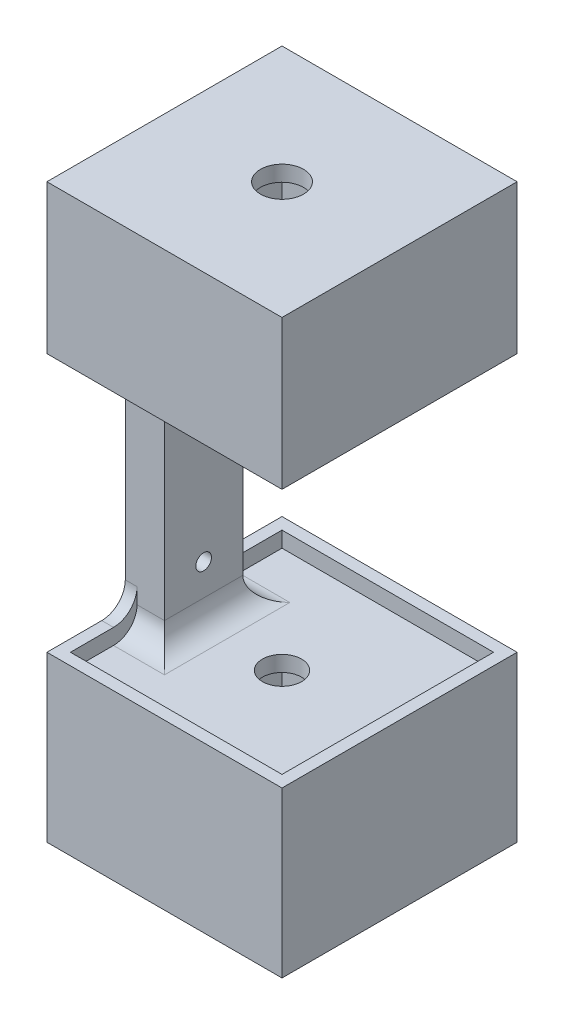
SolidWorks part; units mm, degrees
ref_plane "Спереди" through (0, 0, 0) normal (0, 0, 1) x (1, 0, 0)
ref_plane "Сверху" through (0, 0, 0) normal (0, 1, 0) x (1, 0, 0)
ref_plane "Справа" through (0, 0, 0) normal (1, 0, 0) x (0, 0, -1)
sketch "Эскиз2" plane through (0, 0, 0) normal (0, 1, 0) x (1, 0, 0)
  line L1 (-15, 15) -> (15, 15)
  line L2 (-15, 15) -> (-15, -15)
  line L3 (-15, -15) -> (15, -15)
  line L4 (15, 15) -> (15, -15)
  line L5 (-15, 15) -> (15, -15) construction
  line L6 (-15, -15) -> (15, 15) construction
  point P0 (0, 0)
  dimension "D1" = 30
  dimension "D2" = 30
extrude "Бобышка-Вытянуть1" add sketch "Эскиз2" along normal blind 2
sketch "Эскиз3" plane through (0, 0, 0) normal (0, -1, 0) x (1, 0, 0)
  line L1 (-15, 15) -> (15, 15)
  line L2 (-15, 15) -> (-15, -15)
  line L3 (-15, -15) -> (15, -15)
  line L4 (15, 15) -> (15, -15)
  line L5 (-15, 15) -> (15, -15) construction
  line L6 (-15, -15) -> (15, 15) construction
  point P0 (0, 0)
extrude "Вытянуть-Тонкостенный2" add sketch "Эскиз3" along normal blind 15 thin thin type one direction reverse wall 2
sketch "Эскиз4" plane through (0, 2, 0) normal (0, 1, 0) x (1, 0, 0)
  line L1 (-13.5, 13.5) -> (13.5, 13.5)
  line L2 (-13.5, 13.5) -> (-13.5, -13.5)
  line L3 (-13.5, -13.5) -> (13.5, -13.5)
  line L4 (13.5, 13.5) -> (13.5, -13.5)
  line L5 (-13.5, 13.5) -> (13.5, -13.5) construction
  line L6 (-13.5, -13.5) -> (13.5, 13.5) construction
  point P0 (0, 0)
  dimension "D1" = 27
  dimension "D2" = 27
extrude "Вытянуть-Тонкостенный3" add sketch "Эскиз4" along normal blind 2 thin thin type one direction wall 1.5
sketch "Эскиз5" plane through (0, 2, 0) normal (0, 1, 0) x (1, 0, 0)
  line L1 (-15, 5) -> (-10, 5)
  line L2 (-15, 5) -> (-15, -5)
  line L3 (-15, -5) -> (-10, -5)
  line L4 (-10, 5) -> (-10, -5)
  line L5 (-15, 5) -> (-10, -5) construction
  line L6 (-15, -5) -> (-10, 5) construction
  point P0 (-12.5, 0)
  point P5 (0, 0)
  dimension "D1" = 5
  dimension "D2" = 10
  dimension "D3" = 12.5
extrude "Бобышка-Вытянуть2" add sketch "Эскиз5" along normal blind 35
sketch "Эскиз6" plane through (-15, 0, 0) normal (-1, 0, 0) x (0, 0, 1)
  line L0 (-5, 37) -> (5, 37) construction
  line L1 (-5, 2) -> (5, 2) construction
  circle A0 centre (0, 29) radius 1
  circle A1 centre (0, 9) radius 1
  point P6 (0, 0)
  dimension "D1" = 2
  dimension "D2" = 2
  dimension "D3" = 20
  dimension "D4" = 8
  dimension "D5" = 7
extrude "Вырез-Вытянуть1" cut sketch "Эскиз6" against normal through all
sketch "Эскиз8" plane through (0, 2, 0) normal (0, 1, 0) x (1, 0, 0)
  circle A0 centre (0, 0) radius 2.5
  point P2 (4.7083, 2.9628)
  point P3 (0, 0)
  dimension "D1" = 5
extrude "Вырез-Вытянуть2" cut sketch "Эскиз8" against normal through all
fillet "Скругление1" radius 3 3 edges at (-10, 2, 0) (-11.75, 2, -5) (-11.75, 2, 5)
fillet "Скругление2" radius 3 2 edges at (-14.25, 4, -5.1716) (-14.25, 4, 5.1716)
sketch "Эскиз9" plane through (0, 37, 0) normal (0, 1, 0) x (1, 0, 0)
  line L1 (-15, 15) -> (15, 15)
  line L2 (-15, 15) -> (-15, -15)
  line L3 (-15, -15) -> (15, -15)
  line L4 (15, 15) -> (15, -15)
  line L5 (-15, 15) -> (15, -15) construction
  line L6 (-15, -15) -> (15, 15) construction
  point P0 (0, 0)
extrude "Бобышка-Вытянуть3" add sketch "Эскиз9" along normal blind 2
sketch "Эскиз10" plane through (0, 39, 0) normal (0, 1, 0) x (1, 0, 0)
  line L1 (-15, 15) -> (15, 15)
  line L2 (-15, 15) -> (-15, -15)
  line L3 (-15, -15) -> (15, -15)
  line L4 (15, 15) -> (15, -15)
  line L5 (-15, 15) -> (15, -15) construction
  line L6 (-15, -15) -> (15, 15) construction
  point P0 (0, 0)
extrude "Вытянуть-Тонкостенный4" add sketch "Эскиз10" along normal blind 15 thin thin type one direction reverse wall 2
sketch "Эскиз11" plane through (0, 39, 0) normal (0, 1, 0) x (1, 0, 0)
  circle A0 centre (0, 0) radius 1.75
  dimension "D1" = 3.5
extrude "Вырез-Вытянуть3" cut sketch "Эскиз11" against normal blind 3
fillet "Скругление3" radius 3 3 edges at (-12.5, 37, -5) (-10, 37, 0) (-12.5, 37, 5)
sketch "Эскиз12" plane through (-15, 0, 0) normal (-1, 0, 0) x (0, 0, 1)
  line L1 (-18.8022, 54) -> (-18.8022, -15.0327)
  dimension "D1" = 69.0327
sketch "Эскиз13" plane through (0, -15, 0) normal (0, -1, 0) x (1, 0, 0)
  line L1 (-15, 15) -> (15, 15)
  line L2 (-15, 15) -> (-15, -15)
  line L3 (-15, -15) -> (15, -15)
  line L4 (15, 15) -> (15, -15)
  line L5 (-15, 15) -> (15, -15) construction
  line L6 (-15, -15) -> (15, 15) construction
  point P0 (0, 0)
extrude "Бобышка-Вытянуть4" add sketch "Эскиз13" along normal blind 2
sketch "Эскиз14" plane through (0, 54, 0) normal (0, 1, 0) x (1, 0, 0)
  line L1 (-15, 15) -> (15, 15)
  line L2 (-15, 15) -> (-15, -15)
  line L3 (-15, -15) -> (15, -15)
  line L4 (15, 15) -> (15, -15)
  line L5 (-15, 15) -> (15, -15) construction
  line L6 (-15, -15) -> (15, 15) construction
  point P0 (0, 0)
extrude "Бобышка-Вытянуть5" add sketch "Эскиз14" along normal blind 2
sketch "Эскиз15" plane through (0, 56, 0) normal (0, 1, 0) x (1, 0, 0)
  circle A0 centre (0, 0) radius 2.75
  dimension "D1" = 5.5
extrude "Вырез-Вытянуть4" cut sketch "Эскиз15" against normal blind 2
